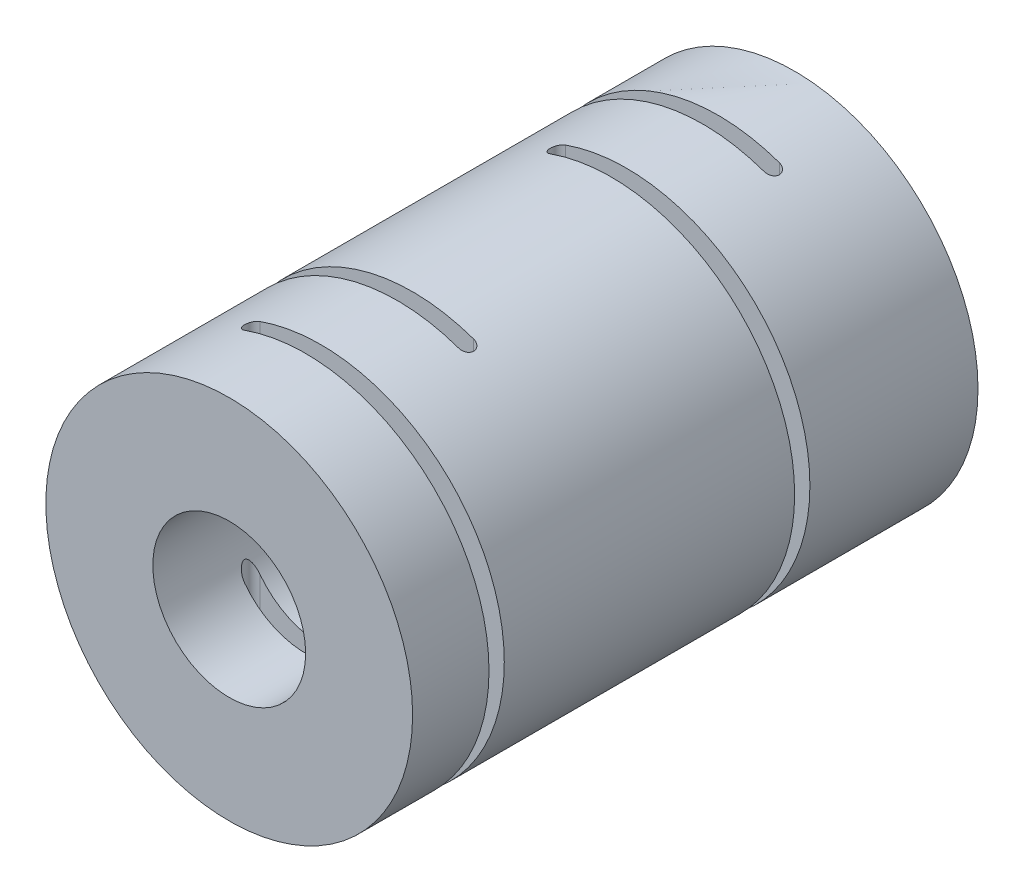
SolidWorks part; units mm, degrees
ref_plane "정면" through (0, 0, 0) normal (0, 0, 1) x (1, 0, 0)
ref_plane "윗면" through (0, 0, 0) normal (0, 1, 0) x (1, 0, 0)
ref_plane "우측면" through (0, 0, 0) normal (1, 0, 0) x (0, 0, -1)
sketch "스케치1" plane through (0, 0, 0) normal (0, 0, 1) x (1, 0, 0)
  circle A0 centre (0, 0) radius 2
  circle A1 centre (0, 0) radius 6
  dimension "D1" = 4
  dimension "D2" = 12
extrude "보스-돌출1" add sketch "스케치1" along normal blind 9.25
sketch "스케치2" plane through (0, 0, 9.25) normal (0, 0, 1) x (1, 0, 0)
  circle A0 centre (0, 0) radius 2.5
  circle A1 centre (0, 0) radius 6
  dimension "D1" = 5
extrude "보스-돌출2" add sketch "스케치2" along normal blind 9.25
sketch "스케치3" plane through (0, 0, 0) normal (0, 1, 0) x (1, 0, 0)
  line L0 (-6, -2.5) -> (2, -2.5)
  line L1 (-6, 0) -> (-6, -18.5) construction
  line L2 (-6, -2.5) -> (-6, -3)
  line L3 (-6, -3) -> (2, -3)
  line L4 (6, 0) -> (-6, 0) construction
  line L5 (-6, -12.5) -> (2, -12.5)
  line L6 (-6, -13) -> (2, -13)
  line L7 (-6, -13) -> (-6, -12.5)
  line L8 (6, -18.5) -> (6, 0) construction
  line L9 (6, -6) -> (-2, -6)
  line L10 (6, -5.5) -> (-2, -5.5)
  line L11 (6, -5.5) -> (6, -6)
  line L12 (6, -16) -> (-2, -16)
  line L13 (6, -16) -> (6, -15.5)
  line L14 (6, -15.5) -> (-2, -15.5)
  arc A0 (2, -2.5) -> (2, -3) centre (2, -2.75) cw
  arc A1 (2, -12.5) -> (2, -13) centre (2, -12.75) cw
  arc A2 (-2, -6) -> (-2, -5.5) centre (-2, -5.75) cw
  arc A3 (-2, -16) -> (-2, -15.5) centre (-2, -15.75) cw
  point P8 (0, -9.25)
  point P29 (0, -9.25)
  dimension "D3" = 8
  dimension "D1" = 0.5
  dimension "D2" = 2.5
  dimension "D5" = 9.25
  dimension "D6" = 6
  dimension "D4" = 2
  dimension "D7" = 2
extrude "컷-돌출1" cut sketch "스케치3" against normal blind 10 and the other way blind 10
ref_plane "평면1" through (0, 0, 9.25) normal (0, 0, 1) x (1, 0, 0)
